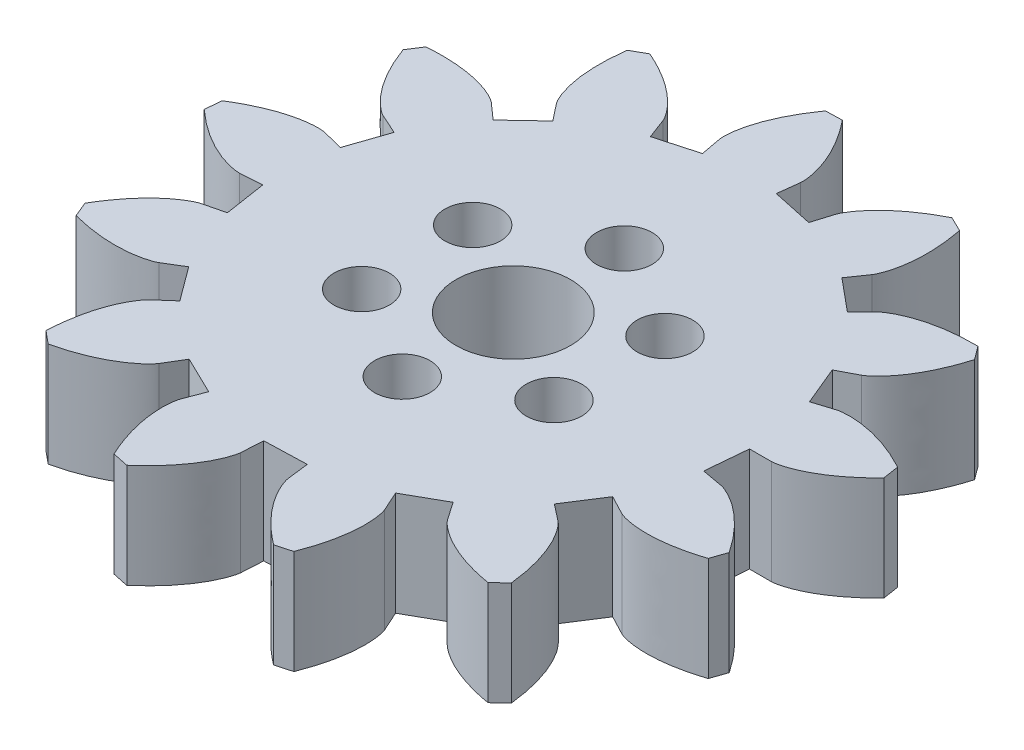
SolidWorks part; units mm, degrees
ref_plane "Front Plane" through (0, 0, 0) normal (0, 0, 1) x (1, 0, 0)
ref_plane "Top Plane" through (0, 0, 0) normal (0, 1, 0) x (1, 0, 0)
ref_plane "Right Plane" through (0, 0, 0) normal (1, 0, 0) x (0, 0, -1)
sketch "Sketch1" plane through (0, 0, 0) normal (0, 1, 0) x (1, 0, 0)
  circle A0 centre (0, 0) radius 8.2743 construction
  circle A1 centre (0, 0) radius 8.2743
  circle A3 centre (-2.7713, -1.6) radius 0.8
  circle A4 centre (-2.7713, -1.6) radius 0.8
  circle A5 centre (0, -3.2) radius 0.8
  circle A6 centre (0, -3.2) radius 0.8
  circle A7 centre (2.7713, -1.6) radius 0.8
  circle A8 centre (2.7713, -1.6) radius 0.8
  circle A9 centre (2.7713, 1.6) radius 0.8
  circle A10 centre (2.7713, 1.6) radius 0.8
  circle A11 centre (0, 3.2) radius 0.8
  circle A12 centre (0, 3.2) radius 0.8
  circle A13 centre (-2.7713, 1.6) radius 0.8
  circle A14 centre (-2.7713, 1.6) radius 0.8
  dimension "D1" = 0
  dimension "D2" = 0
  dimension "D3" = 0
  dimension "D4" = 0
  dimension "D5" = 0
  dimension "D6" = 0
sketch "Sketch2" plane through (0, 0, 0) normal (0, 1, 0) x (1, 0, 0)
  line L0 (6.8098, 0) -> (7.4374, 0)
  line L1 (7.4374, 0) -> (7.4435, 0.0002)
  line L2 (7.4435, 0.0002) -> (7.455, 0.0009)
  line L3 (7.455, 0.0009) -> (7.4719, 0.0023)
  line L4 (7.4719, 0.0023) -> (7.494, 0.0048)
  line L5 (7.494, 0.0048) -> (7.5213, 0.0086)
  line L6 (7.5213, 0.0086) -> (7.5538, 0.0141)
  line L7 (7.5538, 0.0141) -> (7.5915, 0.0214)
  line L8 (7.5915, 0.0214) -> (7.6341, 0.0309)
  line L9 (7.6341, 0.0309) -> (7.6817, 0.0428)
  line L10 (7.6817, 0.0428) -> (7.7341, 0.0575)
  line L11 (7.7341, 0.0575) -> (7.7912, 0.0751)
  line L12 (7.7912, 0.0751) -> (7.8529, 0.096)
  line L13 (7.8529, 0.096) -> (7.9191, 0.1204)
  line L14 (7.9191, 0.1204) -> (7.9895, 0.1486)
  line L15 (7.9895, 0.1486) -> (8.0641, 0.1807)
  line L16 (8.0641, 0.1807) -> (8.1427, 0.2171)
  line L17 (8.1427, 0.2171) -> (8.225, 0.258)
  line L18 (8.225, 0.258) -> (8.311, 0.3036)
  line L19 (8.311, 0.3036) -> (8.4004, 0.3541)
  line L20 (8.4004, 0.3541) -> (8.493, 0.4097)
  line L21 (8.493, 0.4097) -> (8.5886, 0.4707)
  line L22 (8.5886, 0.4707) -> (8.6869, 0.5373)
  line L23 (8.6869, 0.5373) -> (8.7878, 0.6095)
  line L24 (8.7878, 0.6095) -> (8.891, 0.6877)
  line L25 (8.891, 0.6877) -> (8.9962, 0.772)
  line L26 (8.9962, 0.772) -> (9.1033, 0.8626)
  line L27 (9.1033, 0.8626) -> (9.2118, 0.9596)
  line L28 (9.2118, 0.9596) -> (9.3216, 1.0631)
  line L29 (9.3216, 1.0631) -> (9.4324, 1.1733)
  line L30 (9.4324, 1.1733) -> (9.4602, 1.2019)
  line L31 (9.4602, 1.2019) -> (9.4672, 1.2092)
  line L32 (9.4672, 1.2092) -> (9.4689, 1.211)
  line L33 (9.4689, 1.211) -> (9.4692, 1.2112)
  line L34 (9.4692, 1.2112) -> (9.4693, 1.2114)
  line L35 (9.4693, 1.2114) -> (9.3971, 1.6821)
  line L36 (9.3971, 1.6821) -> (9.3969, 1.6823)
  line L37 (9.3969, 1.6823) -> (9.3966, 1.6825)
  line L38 (9.3966, 1.6825) -> (9.3944, 1.6837)
  line L39 (9.3944, 1.6837) -> (9.3856, 1.6885)
  line L40 (9.3856, 1.6885) -> (9.3505, 1.7074)
  line L41 (9.3505, 1.7074) -> (9.2118, 1.7794)
  line L42 (9.2118, 1.7794) -> (9.076, 1.8452)
  line L43 (9.076, 1.8452) -> (8.9434, 1.9052)
  line L44 (8.9434, 1.9052) -> (8.8141, 1.9595)
  line L45 (8.8141, 1.9595) -> (8.6884, 2.0084)
  line L46 (8.6884, 2.0084) -> (8.5666, 2.0521)
  line L47 (8.5666, 2.0521) -> (8.4487, 2.0908)
  line L48 (8.4487, 2.0908) -> (8.3349, 2.1248)
  line L49 (8.3349, 2.1248) -> (8.2254, 2.1544)
  line L50 (8.2254, 2.1544) -> (8.1204, 2.1797)
  line L51 (8.1204, 2.1797) -> (8.02, 2.2011)
  line L52 (8.02, 2.2011) -> (7.9243, 2.2189)
  line L53 (7.9243, 2.2189) -> (7.8335, 2.2332)
  line L54 (7.8335, 2.2332) -> (7.7476, 2.2443)
  line L55 (7.7476, 2.2443) -> (7.6668, 2.2527)
  line L56 (7.6668, 2.2527) -> (7.5912, 2.2584)
  line L57 (7.5912, 2.2584) -> (7.5207, 2.2618)
  line L58 (7.5207, 2.2618) -> (7.4556, 2.2633)
  line L59 (7.4556, 2.2633) -> (7.3958, 2.263)
  line L60 (7.3958, 2.263) -> (7.3415, 2.2613)
  line L61 (7.3415, 2.2613) -> (7.2925, 2.2584)
  line L62 (7.2925, 2.2584) -> (7.2489, 2.2547)
  line L63 (7.2489, 2.2547) -> (7.2109, 2.2504)
  line L64 (7.2109, 2.2504) -> (7.1782, 2.2458)
  line L65 (7.1782, 2.2458) -> (7.151, 2.2413)
  line L66 (7.151, 2.2413) -> (7.1291, 2.237)
  line L67 (7.1291, 2.237) -> (7.1126, 2.2334)
  line L68 (7.1126, 2.2334) -> (7.1015, 2.2306)
  line L69 (7.1015, 2.2306) -> (7.0955, 2.2289)
  line L70 (7.0955, 2.2289) -> (6.4968, 2.0408)
  line L71 (6.4968, 2.0408) -> (6.0298, 3.1647)
  line L72 (6.0298, 3.1647) -> (6.5855, 3.4563)
  line L73 (6.5855, 3.4563) -> (6.5908, 3.4594)
  line L74 (6.5908, 3.4594) -> (6.6007, 3.4653)
  line L75 (6.6007, 3.4653) -> (6.6149, 3.4744)
  line L76 (6.6149, 3.4744) -> (6.6333, 3.4869)
  line L77 (6.6333, 3.4869) -> (6.6558, 3.503)
  line L78 (6.6558, 3.503) -> (6.6821, 3.5229)
  line L79 (6.6821, 3.5229) -> (6.712, 3.5469)
  line L80 (6.712, 3.5469) -> (6.7453, 3.5751)
  line L81 (6.7453, 3.5751) -> (6.7819, 3.6078)
  line L82 (6.7819, 3.6078) -> (6.8215, 3.6451)
  line L83 (6.8215, 3.6451) -> (6.8639, 3.6873)
  line L84 (6.8639, 3.6873) -> (6.9088, 3.7345)
  line L85 (6.9088, 3.7345) -> (6.956, 3.7868)
  line L86 (6.956, 3.7868) -> (7.0053, 3.8445)
  line L87 (7.0053, 3.8445) -> (7.0564, 3.9076)
  line L88 (7.0564, 3.9076) -> (7.1091, 3.9763)
  line L89 (7.1091, 3.9763) -> (7.163, 4.0508)
  line L90 (7.163, 4.0508) -> (7.218, 4.1311)
  line L91 (7.218, 4.1311) -> (7.2736, 4.2174)
  line L92 (7.2736, 4.2174) -> (7.3298, 4.3097)
  line L93 (7.3298, 4.3097) -> (7.3861, 4.4081)
  line L94 (7.3861, 4.4081) -> (7.4422, 4.5127)
  line L95 (7.4422, 4.5127) -> (7.498, 4.6236)
  line L96 (7.498, 4.6236) -> (7.553, 4.7408)
  line L97 (7.553, 4.7408) -> (7.607, 4.8644)
  line L98 (7.607, 4.8644) -> (7.6597, 4.9943)
  line L99 (7.6597, 4.9943) -> (7.7107, 5.1306)
  line L100 (7.7107, 5.1306) -> (7.7598, 5.2733)
  line L101 (7.7598, 5.2733) -> (7.8067, 5.4224)
  line L102 (7.8067, 5.4224) -> (7.8181, 5.4607)
  line L103 (7.8181, 5.4607) -> (7.8209, 5.4703)
  line L104 (7.8209, 5.4703) -> (7.8216, 5.4727)
  line L105 (7.8216, 5.4727) -> (7.8217, 5.473)
  line L106 (7.8217, 5.473) -> (7.8216, 5.4732)
  line L107 (7.8216, 5.4732) -> (7.539, 5.8565)
  line L108 (7.539, 5.8565) -> (7.5387, 5.8566)
  line L109 (7.5387, 5.8566) -> (7.5384, 5.8566)
  line L110 (7.5384, 5.8566) -> (7.5359, 5.8566)
  line L111 (7.5359, 5.8566) -> (7.5259, 5.8568)
  line L112 (7.5259, 5.8568) -> (7.486, 5.8572)
  line L113 (7.486, 5.8572) -> (7.3297, 5.8565)
  line L114 (7.3297, 5.8565) -> (7.1789, 5.8517)
  line L115 (7.1789, 5.8517) -> (7.0336, 5.8432)
  line L116 (7.0336, 5.8432) -> (6.8939, 5.8312)
  line L117 (6.8939, 5.8312) -> (6.7599, 5.8161)
  line L118 (6.7599, 5.8161) -> (6.6317, 5.7981)
  line L119 (6.6317, 5.7981) -> (6.5093, 5.7776)
  line L120 (6.5093, 5.7776) -> (6.3927, 5.7549)
  line L121 (6.3927, 5.7549) -> (6.282, 5.7302)
  line L122 (6.282, 5.7302) -> (6.1773, 5.7038)
  line L123 (6.1773, 5.7038) -> (6.0784, 5.6761)
  line L124 (6.0784, 5.6761) -> (5.9855, 5.6473)
  line L125 (5.9855, 5.6473) -> (5.8984, 5.6178)
  line L126 (5.8984, 5.6178) -> (5.8172, 5.5878)
  line L127 (5.8172, 5.5878) -> (5.7418, 5.5576)
  line L128 (5.7418, 5.5576) -> (5.6721, 5.5275)
  line L129 (5.6721, 5.5275) -> (5.6082, 5.4978)
  line L130 (5.6082, 5.4978) -> (5.5498, 5.4688)
  line L131 (5.5498, 5.4688) -> (5.497, 5.4408)
  line L132 (5.497, 5.4408) -> (5.4497, 5.414)
  line L133 (5.4497, 5.414) -> (5.4076, 5.3887)
  line L134 (5.4076, 5.3887) -> (5.3708, 5.3652)
  line L135 (5.3708, 5.3652) -> (5.3391, 5.3437)
  line L136 (5.3391, 5.3437) -> (5.3123, 5.3245)
  line L137 (5.3123, 5.3245) -> (5.2903, 5.3078)
  line L138 (5.2903, 5.3078) -> (5.2729, 5.2939)
  line L139 (5.2729, 5.2939) -> (5.26, 5.283)
  line L140 (5.26, 5.283) -> (5.2514, 5.2753)
  line L141 (5.2514, 5.2753) -> (5.247, 5.2711)
  line L142 (5.247, 5.2711) -> (4.8042, 4.8263)
  line L143 (4.8042, 4.8263) -> (3.8684, 5.6043)
  line L144 (3.8684, 5.6043) -> (4.2249, 6.1208)
  line L145 (4.2249, 6.1208) -> (4.2282, 6.126)
  line L146 (4.2282, 6.126) -> (4.2342, 6.1359)
  line L147 (4.2342, 6.1359) -> (4.2426, 6.1505)
  line L148 (4.2426, 6.1505) -> (4.2531, 6.1702)
  line L149 (4.2531, 6.1702) -> (4.2655, 6.1948)
  line L150 (4.2655, 6.1948) -> (4.2795, 6.2247)
  line L151 (4.2795, 6.2247) -> (4.2948, 6.2598)
  line L152 (4.2948, 6.2598) -> (4.3112, 6.3003)
  line L153 (4.3112, 6.3003) -> (4.3284, 6.3462)
  line L154 (4.3284, 6.3462) -> (4.3462, 6.3977)
  line L155 (4.3462, 6.3977) -> (4.3641, 6.4547)
  line L156 (4.3641, 6.4547) -> (4.3819, 6.5174)
  line L157 (4.3819, 6.5174) -> (4.3994, 6.5857)
  line L158 (4.3994, 6.5857) -> (4.4163, 6.6596)
  line L159 (4.4163, 6.6596) -> (4.4322, 6.7393)
  line L160 (4.4322, 6.7393) -> (4.4469, 6.8246)
  line L161 (4.4469, 6.8246) -> (4.46, 6.9156)
  line L162 (4.46, 6.9156) -> (4.4714, 7.0123)
  line L163 (4.4714, 7.0123) -> (4.4806, 7.1145)
  line L164 (4.4806, 7.1145) -> (4.4874, 7.2223)
  line L165 (4.4874, 7.2223) -> (4.4915, 7.3356)
  line L166 (4.4915, 7.3356) -> (4.4926, 7.4544)
  line L167 (4.4926, 7.4544) -> (4.4904, 7.5785)
  line L168 (4.4904, 7.5785) -> (4.4847, 7.7078)
  line L169 (4.4847, 7.7078) -> (4.4751, 7.8423)
  line L170 (4.4751, 7.8423) -> (4.4613, 7.9819)
  line L171 (4.4613, 7.9819) -> (4.4432, 8.1263)
  line L172 (4.4432, 8.1263) -> (4.4204, 8.2755)
  line L173 (4.4204, 8.2755) -> (4.3926, 8.4293)
  line L174 (4.3926, 8.4293) -> (4.3849, 8.4684)
  line L175 (4.3849, 8.4684) -> (4.3829, 8.4782)
  line L176 (4.3829, 8.4782) -> (4.3824, 8.4807)
  line L177 (4.3824, 8.4807) -> (4.3823, 8.481)
  line L178 (4.3823, 8.481) -> (4.3822, 8.4812)
  line L179 (4.3822, 8.4812) -> (3.9538, 8.6892)
  line L180 (3.9538, 8.6892) -> (3.9535, 8.6892)
  line L181 (3.9535, 8.6892) -> (3.9533, 8.689)
  line L182 (3.9533, 8.689) -> (3.951, 8.6879)
  line L183 (3.951, 8.6879) -> (3.9421, 8.6834)
  line L184 (3.9421, 8.6834) -> (3.9065, 8.6652)
  line L185 (3.9065, 8.6652) -> (3.7685, 8.5919)
  line L186 (3.7685, 8.5919) -> (3.6371, 8.5176)
  line L187 (3.6371, 8.5176) -> (3.5125, 8.4425)
  line L188 (3.5125, 8.4425) -> (3.3943, 8.367)
  line L189 (3.3943, 8.367) -> (3.2827, 8.2914)
  line L190 (3.2827, 8.2914) -> (3.1775, 8.2159)
  line L191 (3.1775, 8.2159) -> (3.0787, 8.1408)
  line L192 (3.0787, 8.1408) -> (2.986, 8.0665)
  line L193 (2.986, 8.0665) -> (2.8995, 7.9932)
  line L194 (2.8995, 7.9932) -> (2.819, 7.9212)
  line L195 (2.819, 7.9212) -> (2.7444, 7.8507)
  line L196 (2.7444, 7.8507) -> (2.6754, 7.782)
  line L197 (2.6754, 7.782) -> (2.6121, 7.7154)
  line L198 (2.6121, 7.7154) -> (2.5541, 7.6511)
  line L199 (2.5541, 7.6511) -> (2.5013, 7.5893)
  line L200 (2.5013, 7.5893) -> (2.4537, 7.5303)
  line L201 (2.4537, 7.5303) -> (2.4108, 7.4743)
  line L202 (2.4108, 7.4743) -> (2.3726, 7.4215)
  line L203 (2.3726, 7.4215) -> (2.3389, 7.3722)
  line L204 (2.3389, 7.3722) -> (2.3094, 7.3265)
  line L205 (2.3094, 7.3265) -> (2.284, 7.2845)
  line L206 (2.284, 7.2845) -> (2.2623, 7.2466)
  line L207 (2.2623, 7.2466) -> (2.2442, 7.2128)
  line L208 (2.2442, 7.2128) -> (2.2294, 7.1833)
  line L209 (2.2294, 7.1833) -> (2.2177, 7.1583)
  line L210 (2.2177, 7.1583) -> (2.2088, 7.1379)
  line L211 (2.2088, 7.1379) -> (2.2024, 7.1223)
  line L212 (2.2024, 7.1223) -> (2.1984, 7.1115)
  line L213 (2.1984, 7.1115) -> (2.1964, 7.1057)
  line L214 (2.1964, 7.1057) -> (2.011, 6.5061)
  line L215 (2.011, 6.5061) -> (0.8208, 6.7601)
  line L216 (0.8208, 6.7601) -> (0.8965, 7.3831)
  line L217 (0.8965, 7.3831) -> (0.897, 7.3893)
  line L218 (0.897, 7.3893) -> (0.8977, 7.4008)
  line L219 (0.8977, 7.4008) -> (0.8983, 7.4177)
  line L220 (0.8983, 7.4177) -> (0.8985, 7.4399)
  line L221 (0.8985, 7.4399) -> (0.898, 7.4675)
  line L222 (0.898, 7.4675) -> (0.8965, 7.5005)
  line L223 (0.8965, 7.5005) -> (0.8938, 7.5387)
  line L224 (0.8938, 7.5387) -> (0.8895, 7.5822)
  line L225 (0.8895, 7.5822) -> (0.8834, 7.6309)
  line L226 (0.8834, 7.6309) -> (0.8752, 7.6846)
  line L227 (0.8752, 7.6846) -> (0.8645, 7.7435)
  line L228 (0.8645, 7.7435) -> (0.8512, 7.8072)
  line L229 (0.8512, 7.8072) -> (0.835, 7.8758)
  line L230 (0.835, 7.8758) -> (0.8156, 7.9492)
  line L231 (0.8156, 7.9492) -> (0.7926, 8.0271)
  line L232 (0.7926, 8.0271) -> (0.766, 8.1095)
  line L233 (0.766, 8.1095) -> (0.7353, 8.1962)
  line L234 (0.7353, 8.1962) -> (0.7004, 8.287)
  line L235 (0.7004, 8.287) -> (0.6611, 8.3818)
  line L236 (0.6611, 8.3818) -> (0.617, 8.4804)
  line L237 (0.617, 8.4804) -> (0.568, 8.5827)
  line L238 (0.568, 8.5827) -> (0.5138, 8.6883)
  line L239 (0.5138, 8.6883) -> (0.4542, 8.7972)
  line L240 (0.4542, 8.7972) -> (0.389, 8.9091)
  line L241 (0.389, 8.9091) -> (0.318, 9.0237)
  line L242 (0.318, 9.0237) -> (0.241, 9.1409)
  line L243 (0.241, 9.1409) -> (0.1578, 9.2603)
  line L244 (0.1578, 9.2603) -> (0.0682, 9.3818)
  line L245 (0.0682, 9.3818) -> (-0.0278, 9.5051)
  line L246 (-0.0278, 9.5051) -> (-0.0529, 9.5361)
  line L247 (-0.0529, 9.5361) -> (-0.0592, 9.5439)
  line L248 (-0.0592, 9.5439) -> (-0.0608, 9.5459)
  line L249 (-0.0608, 9.5459) -> (-0.061, 9.5461)
  line L250 (-0.061, 9.5461) -> (-0.0612, 9.5462)
  line L251 (-0.0612, 9.5462) -> (-0.5372, 9.5313)
  line L252 (-0.5372, 9.5313) -> (-0.5374, 9.5312)
  line L253 (-0.5374, 9.5312) -> (-0.5375, 9.5309)
  line L254 (-0.5375, 9.5309) -> (-0.539, 9.5289)
  line L255 (-0.539, 9.5289) -> (-0.5448, 9.5207)
  line L256 (-0.5448, 9.5207) -> (-0.5679, 9.4881)
  line L257 (-0.5679, 9.4881) -> (-0.656, 9.3591)
  line L258 (-0.656, 9.3591) -> (-0.7378, 9.2322)
  line L259 (-0.7378, 9.2322) -> (-0.8133, 9.1078)
  line L260 (-0.8133, 9.1078) -> (-0.8828, 8.986)
  line L261 (-0.8828, 8.986) -> (-0.9465, 8.8672)
  line L262 (-0.9465, 8.8672) -> (-1.0046, 8.7515)
  line L263 (-1.0046, 8.7515) -> (-1.0572, 8.6391)
  line L264 (-1.0572, 8.6391) -> (-1.1047, 8.5302)
  line L265 (-1.1047, 8.5302) -> (-1.1472, 8.4251)
  line L266 (-1.1472, 8.4251) -> (-1.185, 8.3239)
  line L267 (-1.185, 8.3239) -> (-1.2184, 8.2268)
  line L268 (-1.2184, 8.2268) -> (-1.2475, 8.134)
  line L269 (-1.2475, 8.134) -> (-1.2727, 8.0455)
  line L270 (-1.2727, 8.0455) -> (-1.2941, 7.9616)
  line L271 (-1.2941, 7.9616) -> (-1.3121, 7.8824)
  line L272 (-1.3121, 7.8824) -> (-1.3269, 7.808)
  line L273 (-1.3269, 7.808) -> (-1.3388, 7.7385)
  line L274 (-1.3388, 7.7385) -> (-1.3481, 7.6741)
  line L275 (-1.3481, 7.6741) -> (-1.355, 7.6147)
  line L276 (-1.355, 7.6147) -> (-1.3599, 7.5605)
  line L277 (-1.3599, 7.5605) -> (-1.3629, 7.5115)
  line L278 (-1.3629, 7.5115) -> (-1.3645, 7.4679)
  line L279 (-1.3645, 7.4679) -> (-1.3648, 7.4295)
  line L280 (-1.3648, 7.4295) -> (-1.3642, 7.3966)
  line L281 (-1.3642, 7.3966) -> (-1.363, 7.369)
  line L282 (-1.363, 7.369) -> (-1.3614, 7.3468)
  line L283 (-1.3614, 7.3468) -> (-1.3597, 7.33)
  line L284 (-1.3597, 7.33) -> (-1.3583, 7.3186)
  line L285 (-1.3583, 7.3186) -> (-1.3574, 7.3125)
  line L286 (-1.3574, 7.3125) -> (-1.2429, 6.6954)
  line L287 (-1.2429, 6.6954) -> (-2.4148, 6.3673)
  line L288 (-2.4148, 6.3673) -> (-2.6373, 6.9541)
  line L289 (-2.6373, 6.9541) -> (-2.6397, 6.9598)
  line L290 (-2.6397, 6.9598) -> (-2.6444, 6.9703)
  line L291 (-2.6444, 6.9703) -> (-2.6517, 6.9855)
  line L292 (-2.6517, 6.9855) -> (-2.6619, 7.0053)
  line L293 (-2.6619, 7.0053) -> (-2.6752, 7.0295)
  line L294 (-2.6752, 7.0295) -> (-2.6918, 7.058)
  line L295 (-2.6918, 7.058) -> (-2.712, 7.0906)
  line L296 (-2.712, 7.0906) -> (-2.736, 7.1271)
  line L297 (-2.736, 7.1271) -> (-2.764, 7.1673)
  line L298 (-2.764, 7.1673) -> (-2.7963, 7.2111)
  line L299 (-2.7963, 7.2111) -> (-2.8331, 7.2583)
  line L300 (-2.8331, 7.2583) -> (-2.8745, 7.3086)
  line L301 (-2.8745, 7.3086) -> (-2.9207, 7.3618)
  line L302 (-2.9207, 7.3618) -> (-2.972, 7.4176)
  line L303 (-2.972, 7.4176) -> (-3.0285, 7.476)
  line L304 (-3.0285, 7.476) -> (-3.0904, 7.5365)
  line L305 (-3.0904, 7.5365) -> (-3.1578, 7.5991)
  line L306 (-3.1578, 7.5991) -> (-3.2309, 7.6633)
  line L307 (-3.2309, 7.6633) -> (-3.3099, 7.729)
  line L308 (-3.3099, 7.729) -> (-3.3947, 7.7958)
  line L309 (-3.3947, 7.7958) -> (-3.4857, 7.8635)
  line L310 (-3.4857, 7.8635) -> (-3.5828, 7.9319)
  line L311 (-3.5828, 7.9319) -> (-3.6861, 8.0006)
  line L312 (-3.6861, 8.0006) -> (-3.7958, 8.0694)
  line L313 (-3.7958, 8.0694) -> (-3.912, 8.1379)
  line L314 (-3.912, 8.1379) -> (-4.0346, 8.2058)
  line L315 (-4.0346, 8.2058) -> (-4.1638, 8.2729)
  line L316 (-4.1638, 8.2729) -> (-4.2995, 8.3389)
  line L317 (-4.2995, 8.3389) -> (-4.4419, 8.4034)
  line L318 (-4.4419, 8.4034) -> (-4.4785, 8.4193)
  line L319 (-4.4785, 8.4193) -> (-4.4877, 8.4232)
  line L320 (-4.4877, 8.4232) -> (-4.49, 8.4242)
  line L321 (-4.49, 8.4242) -> (-4.4903, 8.4243)
  line L322 (-4.4903, 8.4243) -> (-4.4905, 8.4243)
  line L323 (-4.4905, 8.4243) -> (-4.9051, 8.1899)
  line L324 (-4.9051, 8.1899) -> (-4.9052, 8.1897)
  line L325 (-4.9052, 8.1897) -> (-4.9052, 8.1894)
  line L326 (-4.9052, 8.1894) -> (-4.9056, 8.1869)
  line L327 (-4.9056, 8.1869) -> (-4.9069, 8.177)
  line L328 (-4.9069, 8.177) -> (-4.9122, 8.1374)
  line L329 (-4.9122, 8.1374) -> (-4.9303, 7.9822)
  line L330 (-4.9303, 7.9822) -> (-4.9437, 7.8319)
  line L331 (-4.9437, 7.8319) -> (-4.9528, 7.6866)
  line L332 (-4.9528, 7.6866) -> (-4.9577, 7.5465)
  line L333 (-4.9577, 7.5465) -> (-4.9589, 7.4116)
  line L334 (-4.9589, 7.4116) -> (-4.9565, 7.2822)
  line L335 (-4.9565, 7.2822) -> (-4.9509, 7.1582)
  line L336 (-4.9509, 7.1582) -> (-4.9424, 7.0398)
  line L337 (-4.9424, 7.0398) -> (-4.9312, 6.9269)
  line L338 (-4.9312, 6.9269) -> (-4.9176, 6.8197)
  line L339 (-4.9176, 6.8197) -> (-4.902, 6.7183)
  line L340 (-4.902, 6.7183) -> (-4.8847, 6.6225)
  line L341 (-4.8847, 6.6225) -> (-4.8658, 6.5325)
  line L342 (-4.8658, 6.5325) -> (-4.8458, 6.4483)
  line L343 (-4.8458, 6.4483) -> (-4.825, 6.3698)
  line L344 (-4.825, 6.3698) -> (-4.8035, 6.297)
  line L345 (-4.8035, 6.297) -> (-4.7818, 6.23)
  line L346 (-4.7818, 6.23) -> (-4.76, 6.1686)
  line L347 (-4.76, 6.1686) -> (-4.7385, 6.1128)
  line L348 (-4.7385, 6.1128) -> (-4.7176, 6.0625)
  line L349 (-4.7176, 6.0625) -> (-4.6976, 6.0177)
  line L350 (-4.6976, 6.0177) -> (-4.6787, 5.9784)
  line L351 (-4.6787, 5.9784) -> (-4.6612, 5.9443)
  line L352 (-4.6612, 5.9443) -> (-4.6453, 5.9154)
  line L353 (-4.6453, 5.9154) -> (-4.6314, 5.8915)
  line L354 (-4.6314, 5.8915) -> (-4.6197, 5.8726)
  line L355 (-4.6197, 5.8726) -> (-4.6104, 5.8585)
  line L356 (-4.6104, 5.8585) -> (-4.6038, 5.849)
  line L357 (-4.6038, 5.849) -> (-4.6002, 5.8441)
  line L358 (-4.6002, 5.8441) -> (-4.212, 5.3509)
  line L359 (-4.212, 5.3509) -> (-5.0972, 4.5157)
  line L360 (-5.0972, 4.5157) -> (-5.567, 4.9319)
  line L361 (-5.567, 4.9319) -> (-5.5717, 4.9358)
  line L362 (-5.5717, 4.9358) -> (-5.5808, 4.9429)
  line L363 (-5.5808, 4.9429) -> (-5.5943, 4.953)
  line L364 (-5.5943, 4.953) -> (-5.6125, 4.9658)
  line L365 (-5.6125, 4.9658) -> (-5.6355, 4.9811)
  line L366 (-5.6355, 4.9811) -> (-5.6635, 4.9986)
  line L367 (-5.6635, 4.9986) -> (-5.6965, 5.0181)
  line L368 (-5.6965, 5.0181) -> (-5.7347, 5.0392)
  line L369 (-5.7347, 5.0392) -> (-5.7782, 5.0618)
  line L370 (-5.7782, 5.0618) -> (-5.8272, 5.0856)
  line L371 (-5.8272, 5.0856) -> (-5.8816, 5.1103)
  line L372 (-5.8816, 5.1103) -> (-5.9417, 5.1356)
  line L373 (-5.9417, 5.1356) -> (-6.0074, 5.1612)
  line L374 (-6.0074, 5.1612) -> (-6.0787, 5.1868)
  line L375 (-6.0787, 5.1868) -> (-6.1559, 5.2122)
  line L376 (-6.1559, 5.2122) -> (-6.2388, 5.2371)
  line L377 (-6.2388, 5.2371) -> (-6.3276, 5.2611)
  line L378 (-6.3276, 5.2611) -> (-6.4222, 5.284)
  line L379 (-6.4222, 5.284) -> (-6.5226, 5.3055)
  line L380 (-6.5226, 5.3055) -> (-6.6288, 5.3252)
  line L381 (-6.6288, 5.3252) -> (-6.7408, 5.3429)
  line L382 (-6.7408, 5.3429) -> (-6.8585, 5.3584)
  line L383 (-6.8585, 5.3584) -> (-6.982, 5.3712)
  line L384 (-6.982, 5.3712) -> (-7.1111, 5.381)
  line L385 (-7.1111, 5.381) -> (-7.2457, 5.3877)
  line L386 (-7.2457, 5.3877) -> (-7.3859, 5.3909)
  line L387 (-7.3859, 5.3909) -> (-7.5315, 5.3903)
  line L388 (-7.5315, 5.3903) -> (-7.6823, 5.3856)
  line L389 (-7.6823, 5.3856) -> (-7.8383, 5.3766)
  line L390 (-7.8383, 5.3766) -> (-7.8781, 5.3736)
  line L391 (-7.8781, 5.3736) -> (-7.8881, 5.3729)
  line L392 (-7.8881, 5.3729) -> (-7.8906, 5.3727)
  line L393 (-7.8906, 5.3727) -> (-7.8909, 5.3726)
  line L394 (-7.8909, 5.3726) -> (-7.8912, 5.3725)
  line L395 (-7.8912, 5.3725) -> (-8.1493, 4.9723)
  line L396 (-8.1493, 4.9723) -> (-8.1493, 4.9721)
  line L397 (-8.1493, 4.9721) -> (-8.1492, 4.9718)
  line L398 (-8.1492, 4.9718) -> (-8.1483, 4.9694)
  line L399 (-8.1483, 4.9694) -> (-8.1449, 4.96)
  line L400 (-8.1449, 4.96) -> (-8.1312, 4.9225)
  line L401 (-8.1312, 4.9225) -> (-8.0751, 4.7767)
  line L402 (-8.0751, 4.7767) -> (-8.0171, 4.6373)
  line L403 (-8.0171, 4.6373) -> (-7.9576, 4.5045)
  line L404 (-7.9576, 4.5045) -> (-7.8969, 4.3781)
  line L405 (-7.8969, 4.3781) -> (-7.8352, 4.2582)
  line L406 (-7.8352, 4.2582) -> (-7.773, 4.1447)
  line L407 (-7.773, 4.1447) -> (-7.7104, 4.0375)
  line L408 (-7.7104, 4.0375) -> (-7.6478, 3.9366)
  line L409 (-7.6478, 3.9366) -> (-7.5854, 3.8419)
  line L410 (-7.5854, 3.8419) -> (-7.5236, 3.7533)
  line L411 (-7.5236, 3.7533) -> (-7.4627, 3.6707)
  line L412 (-7.4627, 3.6707) -> (-7.4028, 3.5939)
  line L413 (-7.4028, 3.5939) -> (-7.3443, 3.523)
  line L414 (-7.3443, 3.523) -> (-7.2874, 3.4577)
  line L415 (-7.2874, 3.4577) -> (-7.2325, 3.3979)
  line L416 (-7.2325, 3.3979) -> (-7.1797, 3.3434)
  line L417 (-7.1797, 3.3434) -> (-7.1292, 3.2942)
  line L418 (-7.1292, 3.2942) -> (-7.0814, 3.2499)
  line L419 (-7.0814, 3.2499) -> (-7.0365, 3.2105)
  line L420 (-7.0365, 3.2105) -> (-6.9947, 3.1757)
  line L421 (-6.9947, 3.1757) -> (-6.9561, 3.1454)
  line L422 (-6.9561, 3.1454) -> (-6.9211, 3.1193)
  line L423 (-6.9211, 3.1193) -> (-6.8897, 3.0972)
  line L424 (-6.8897, 3.0972) -> (-6.8622, 3.079)
  line L425 (-6.8622, 3.079) -> (-6.8388, 3.0643)
  line L426 (-6.8388, 3.0643) -> (-6.8197, 3.0531)
  line L427 (-6.8197, 3.0531) -> (-6.8049, 3.0449)
  line L428 (-6.8049, 3.0449) -> (-6.7947, 3.0395)
  line L429 (-6.7947, 3.0395) -> (-6.7891, 3.0368)
  line L430 (-6.7891, 3.0368) -> (-6.2162, 2.7806)
  line L431 (-6.2162, 2.7806) -> (-6.6119, 1.6297)
  line L432 (-6.6119, 1.6297) -> (-7.2213, 1.7799)
  line L433 (-7.2213, 1.7799) -> (-7.2273, 1.7811)
  line L434 (-7.2273, 1.7811) -> (-7.2386, 1.7832)
  line L435 (-7.2386, 1.7832) -> (-7.2553, 1.7859)
  line L436 (-7.2553, 1.7859) -> (-7.2774, 1.7887)
  line L437 (-7.2774, 1.7887) -> (-7.3048, 1.7916)
  line L438 (-7.3048, 1.7916) -> (-7.3377, 1.7941)
  line L439 (-7.3377, 1.7941) -> (-7.376, 1.796)
  line L440 (-7.376, 1.796) -> (-7.4197, 1.797)
  line L441 (-7.4197, 1.797) -> (-7.4687, 1.7968)
  line L442 (-7.4687, 1.7968) -> (-7.5231, 1.7951)
  line L443 (-7.5231, 1.7951) -> (-7.5828, 1.7916)
  line L444 (-7.5828, 1.7916) -> (-7.6477, 1.7861)
  line L445 (-7.6477, 1.7861) -> (-7.7178, 1.7782)
  line L446 (-7.7178, 1.7782) -> (-7.7929, 1.7678)
  line L447 (-7.7929, 1.7678) -> (-7.873, 1.7544)
  line L448 (-7.873, 1.7544) -> (-7.958, 1.7379)
  line L449 (-7.958, 1.7379) -> (-8.0478, 1.7179)
  line L450 (-8.0478, 1.7179) -> (-8.1421, 1.6942)
  line L451 (-8.1421, 1.6942) -> (-8.241, 1.6666)
  line L452 (-8.241, 1.6666) -> (-8.3442, 1.6347)
  line L453 (-8.3442, 1.6347) -> (-8.4517, 1.5984)
  line L454 (-8.4517, 1.5984) -> (-8.5631, 1.5573)
  line L455 (-8.5631, 1.5573) -> (-8.6783, 1.5112)
  line L456 (-8.6783, 1.5112) -> (-8.7972, 1.46)
  line L457 (-8.7972, 1.46) -> (-8.9196, 1.4033)
  line L458 (-8.9196, 1.4033) -> (-9.0452, 1.341)
  line L459 (-9.0452, 1.341) -> (-9.1738, 1.2728)
  line L460 (-9.1738, 1.2728) -> (-9.3052, 1.1986)
  line L461 (-9.3052, 1.1986) -> (-9.4391, 1.1181)
  line L462 (-9.4391, 1.1181) -> (-9.473, 1.097)
  line L463 (-9.473, 1.097) -> (-9.4815, 1.0916)
  line L464 (-9.4815, 1.0916) -> (-9.4836, 1.0903)
  line L465 (-9.4836, 1.0903) -> (-9.4839, 1.0901)
  line L466 (-9.4839, 1.0901) -> (-9.484, 1.0899)
  line L467 (-9.484, 1.0899) -> (-9.5266, 0.6156)
  line L468 (-9.5266, 0.6156) -> (-9.5265, 0.6154)
  line L469 (-9.5265, 0.6154) -> (-9.5262, 0.6152)
  line L470 (-9.5262, 0.6152) -> (-9.5244, 0.6135)
  line L471 (-9.5244, 0.6135) -> (-9.517, 0.6067)
  line L472 (-9.517, 0.6067) -> (-9.4874, 0.5799)
  line L473 (-9.4874, 0.5799) -> (-9.3699, 0.4769)
  line L474 (-9.3699, 0.4769) -> (-9.2538, 0.3804)
  line L475 (-9.2538, 0.3804) -> (-9.1394, 0.2904)
  line L476 (-9.1394, 0.2904) -> (-9.0269, 0.2068)
  line L477 (-9.0269, 0.2068) -> (-8.9166, 0.1292)
  line L478 (-8.9166, 0.1292) -> (-8.8087, 0.0576)
  line L479 (-8.8087, 0.0576) -> (-8.7035, -0.0082)
  line L480 (-8.7035, -0.0082) -> (-8.6012, -0.0684)
  line L481 (-8.6012, -0.0684) -> (-8.502, -0.1233)
  line L482 (-8.502, -0.1233) -> (-8.4061, -0.1731)
  line L483 (-8.4061, -0.1731) -> (-8.3137, -0.2179)
  line L484 (-8.3137, -0.2179) -> (-8.225, -0.258)
  line L485 (-8.225, -0.258) -> (-8.1403, -0.2936)
  line L486 (-8.1403, -0.2936) -> (-8.0596, -0.325)
  line L487 (-8.0596, -0.325) -> (-7.9831, -0.3524)
  line L488 (-7.9831, -0.3524) -> (-7.911, -0.3761)
  line L489 (-7.911, -0.3761) -> (-7.8435, -0.3963)
  line L490 (-7.8435, -0.3963) -> (-7.7806, -0.4133)
  line L491 (-7.7806, -0.4133) -> (-7.7225, -0.4273)
  line L492 (-7.7225, -0.4273) -> (-7.6693, -0.4386)
  line L493 (-7.6693, -0.4386) -> (-7.6211, -0.4476)
  line L494 (-7.6211, -0.4476) -> (-7.5779, -0.4544)
  line L495 (-7.5779, -0.4544) -> (-7.5399, -0.4593)
  line L496 (-7.5399, -0.4593) -> (-7.5071, -0.4627)
  line L497 (-7.5071, -0.4627) -> (-7.4795, -0.4648)
  line L498 (-7.4795, -0.4648) -> (-7.4573, -0.4659)
  line L499 (-7.4573, -0.4659) -> (-7.4404, -0.4663)
  line L500 (-7.4404, -0.4663) -> (-7.4289, -0.4662)
  line L501 (-7.4289, -0.4662) -> (-7.4228, -0.4661)
  line L502 (-7.4228, -0.4661) -> (-6.7964, -0.4267)
  line L503 (-6.7964, -0.4267) -> (-6.6119, -1.6297)
  line L504 (-6.6119, -1.6297) -> (-7.2213, -1.7799)
  line L505 (-7.2213, -1.7799) -> (-7.2272, -1.7816)
  line L506 (-7.2272, -1.7816) -> (-7.2382, -1.785)
  line L507 (-7.2382, -1.785) -> (-7.2542, -1.7904)
  line L508 (-7.2542, -1.7904) -> (-7.2751, -1.7981)
  line L509 (-7.2751, -1.7981) -> (-7.3007, -1.8084)
  line L510 (-7.3007, -1.8084) -> (-7.331, -1.8214)
  line L511 (-7.331, -1.8214) -> (-7.3658, -1.8375)
  line L512 (-7.3658, -1.8375) -> (-7.4049, -1.857)
  line L513 (-7.4049, -1.857) -> (-7.4482, -1.8799)
  line L514 (-7.4482, -1.8799) -> (-7.4956, -1.9067)
  line L515 (-7.4956, -1.9067) -> (-7.5468, -1.9375)
  line L516 (-7.5468, -1.9375) -> (-7.6017, -1.9726)
  line L517 (-7.6017, -1.9726) -> (-7.6601, -2.0121)
  line L518 (-7.6601, -2.0121) -> (-7.7218, -2.0563)
  line L519 (-7.7218, -2.0563) -> (-7.7865, -2.1053)
  line L520 (-7.7865, -2.1053) -> (-7.8541, -2.1595)
  line L521 (-7.8541, -2.1595) -> (-7.9243, -2.2189)
  line L522 (-7.9243, -2.2189) -> (-7.9969, -2.2837)
  line L523 (-7.9969, -2.2837) -> (-8.0716, -2.3541)
  line L524 (-8.0716, -2.3541) -> (-8.1481, -2.4303)
  line L525 (-8.1481, -2.4303) -> (-8.2264, -2.5124)
  line L526 (-8.2264, -2.5124) -> (-8.3059, -2.6006)
  line L527 (-8.3059, -2.6006) -> (-8.3866, -2.6949)
  line L528 (-8.3866, -2.6949) -> (-8.4681, -2.7955)
  line L529 (-8.4681, -2.7955) -> (-8.5501, -2.9026)
  line L530 (-8.5501, -2.9026) -> (-8.6323, -3.0161)
  line L531 (-8.6323, -3.0161) -> (-8.7145, -3.1362)
  line L532 (-8.7145, -3.1362) -> (-8.7963, -3.263)
  line L533 (-8.7963, -3.263) -> (-8.8775, -3.3966)
  line L534 (-8.8775, -3.3966) -> (-8.8977, -3.431)
  line L535 (-8.8977, -3.431) -> (-8.9027, -3.4397)
  line L536 (-8.9027, -3.4397) -> (-8.904, -3.4418)
  line L537 (-8.904, -3.4418) -> (-8.9041, -3.4421)
  line L538 (-8.9041, -3.4421) -> (-8.9042, -3.4423)
  line L539 (-8.9042, -3.4423) -> (-8.7214, -3.8821)
  line L540 (-8.7214, -3.8821) -> (-8.7213, -3.8822)
  line L541 (-8.7213, -3.8822) -> (-8.7209, -3.8823)
  line L542 (-8.7209, -3.8823) -> (-8.7185, -3.883)
  line L543 (-8.7185, -3.883) -> (-8.7088, -3.8855)
  line L544 (-8.7088, -3.8855) -> (-8.6702, -3.8955)
  line L545 (-8.6702, -3.8955) -> (-8.5183, -3.9322)
  line L546 (-8.5183, -3.9322) -> (-8.3707, -3.9636)
  line L547 (-8.3707, -3.9636) -> (-8.2275, -3.9901)
  line L548 (-8.2275, -3.9901) -> (-8.089, -4.0119)
  line L549 (-8.089, -4.0119) -> (-7.9553, -4.0293)
  line L550 (-7.9553, -4.0293) -> (-7.8265, -4.0426)
  line L551 (-7.8265, -4.0426) -> (-7.7028, -4.052)
  line L552 (-7.7028, -4.052) -> (-7.5842, -4.0578)
  line L553 (-7.5842, -4.0578) -> (-7.4708, -4.0603)
  line L554 (-7.4708, -4.0603) -> (-7.3628, -4.0597)
  line L555 (-7.3628, -4.0597) -> (-7.2602, -4.0565)
  line L556 (-7.2602, -4.0565) -> (-7.163, -4.0508)
  line L557 (-7.163, -4.0508) -> (-7.0714, -4.0429)
  line L558 (-7.0714, -4.0429) -> (-6.9854, -4.0332)
  line L559 (-6.9854, -4.0332) -> (-6.9049, -4.022)
  line L560 (-6.9049, -4.022) -> (-6.8301, -4.0095)
  line L561 (-6.8301, -4.0095) -> (-6.7609, -3.9959)
  line L562 (-6.7609, -3.9959) -> (-6.6973, -3.9818)
  line L563 (-6.6973, -3.9818) -> (-6.6394, -3.9672)
  line L564 (-6.6394, -3.9672) -> (-6.587, -3.9525)
  line L565 (-6.587, -3.9525) -> (-6.5401, -3.938)
  line L566 (-6.5401, -3.938) -> (-6.4987, -3.924)
  line L567 (-6.4987, -3.924) -> (-6.4628, -3.9107)
  line L568 (-6.4628, -3.9107) -> (-6.4322, -3.8984)
  line L569 (-6.4322, -3.8984) -> (-6.4068, -3.8875)
  line L570 (-6.4068, -3.8875) -> (-6.3866, -3.8781)
  line L571 (-6.3866, -3.8781) -> (-6.3715, -3.8706)
  line L572 (-6.3715, -3.8706) -> (-6.3613, -3.8652)
  line L573 (-6.3613, -3.8652) -> (-6.3559, -3.8622)
  line L574 (-6.3559, -3.8622) -> (-5.8196, -3.5363)
  line L575 (-5.8196, -3.5363) -> (-5.0972, -4.5157)
  line L576 (-5.0972, -4.5157) -> (-5.5669, -4.9319)
  line L577 (-5.5669, -4.9319) -> (-5.5714, -4.9361)
  line L578 (-5.5714, -4.9361) -> (-5.5796, -4.9443)
  line L579 (-5.5796, -4.9443) -> (-5.5912, -4.9565)
  line L580 (-5.5912, -4.9565) -> (-5.6061, -4.973)
  line L581 (-5.6061, -4.973) -> (-5.6241, -4.994)
  line L582 (-5.6241, -4.994) -> (-5.6448, -5.0197)
  line L583 (-5.6448, -5.0197) -> (-5.6681, -5.0501)
  line L584 (-5.6681, -5.0501) -> (-5.6937, -5.0855)
  line L585 (-5.6937, -5.0855) -> (-5.7214, -5.126)
  line L586 (-5.7214, -5.126) -> (-5.7509, -5.1717)
  line L587 (-5.7509, -5.1717) -> (-5.782, -5.2228)
  line L588 (-5.782, -5.2228) -> (-5.8143, -5.2793)
  line L589 (-5.8143, -5.2793) -> (-5.8477, -5.3414)
  line L590 (-5.8477, -5.3414) -> (-5.8817, -5.4092)
  line L591 (-5.8817, -5.4092) -> (-5.9162, -5.4828)
  line L592 (-5.9162, -5.4828) -> (-5.9509, -5.5621)
  line L593 (-5.9509, -5.5621) -> (-5.9855, -5.6473)
  line L594 (-5.9855, -5.6473) -> (-6.0196, -5.7384)
  line L595 (-6.0196, -5.7384) -> (-6.053, -5.8355)
  line L596 (-6.053, -5.8355) -> (-6.0854, -5.9386)
  line L597 (-6.0854, -5.9386) -> (-6.1165, -6.0476)
  line L598 (-6.1165, -6.0476) -> (-6.146, -6.1626)
  line L599 (-6.146, -6.1626) -> (-6.1736, -6.2836)
  line L600 (-6.1736, -6.2836) -> (-6.1989, -6.4106)
  line L601 (-6.1989, -6.4106) -> (-6.2218, -6.5435)
  line L602 (-6.2218, -6.5435) -> (-6.2419, -6.6822)
  line L603 (-6.2419, -6.6822) -> (-6.2588, -6.8268)
  line L604 (-6.2588, -6.8268) -> (-6.2724, -6.9771)
  line L605 (-6.2724, -6.9771) -> (-6.2822, -7.1331)
  line L606 (-6.2822, -7.1331) -> (-6.2841, -7.173)
  line L607 (-6.2841, -7.173) -> (-6.2845, -7.183)
  line L608 (-6.2845, -7.183) -> (-6.2846, -7.1855)
  line L609 (-6.2846, -7.1855) -> (-6.2846, -7.1858)
  line L610 (-6.2846, -7.1858) -> (-6.2845, -7.186)
  line L611 (-6.2845, -7.186) -> (-5.9183, -7.4905)
  line L612 (-5.9183, -7.4905) -> (-5.9181, -7.4905)
  line L613 (-5.9181, -7.4905) -> (-5.9178, -7.4905)
  line L614 (-5.9178, -7.4905) -> (-5.9154, -7.4899)
  line L615 (-5.9154, -7.4899) -> (-5.9056, -7.4877)
  line L616 (-5.9056, -7.4877) -> (-5.8667, -7.4786)
  line L617 (-5.8667, -7.4786) -> (-5.7152, -7.4404)
  line L618 (-5.7152, -7.4404) -> (-5.5699, -7.3997)
  line L619 (-5.5699, -7.3997) -> (-5.4308, -7.3566)
  line L620 (-5.4308, -7.3566) -> (-5.298, -7.3116)
  line L621 (-5.298, -7.3116) -> (-5.1716, -7.2648)
  line L622 (-5.1716, -7.2648) -> (-5.0514, -7.2167)
  line L623 (-5.0514, -7.2167) -> (-4.9374, -7.1675)
  line L624 (-4.9374, -7.1675) -> (-4.8297, -7.1175)
  line L625 (-4.8297, -7.1175) -> (-4.7282, -7.067)
  line L626 (-4.7282, -7.067) -> (-4.6328, -7.0164)
  line L627 (-4.6328, -7.0164) -> (-4.5434, -6.9658)
  line L628 (-4.5434, -6.9658) -> (-4.46, -6.9156)
  line L629 (-4.46, -6.9156) -> (-4.3826, -6.8661)
  line L630 (-4.3826, -6.8661) -> (-4.3109, -6.8175)
  line L631 (-4.3109, -6.8175) -> (-4.2449, -6.7702)
  line L632 (-4.2449, -6.7702) -> (-4.1845, -6.7243)
  line L633 (-4.1845, -6.7243) -> (-4.1295, -6.6802)
  line L634 (-4.1295, -6.6802) -> (-4.0798, -6.6381)
  line L635 (-4.0798, -6.6381) -> (-4.0352, -6.5982)
  line L636 (-4.0352, -6.5982) -> (-3.9957, -6.5609)
  line L637 (-3.9957, -6.5609) -> (-3.9609, -6.5263)
  line L638 (-3.9609, -6.5263) -> (-3.9308, -6.4946)
  line L639 (-3.9308, -6.4946) -> (-3.9051, -6.4661)
  line L640 (-3.9051, -6.4661) -> (-3.8837, -6.4411)
  line L641 (-3.8837, -6.4411) -> (-3.8663, -6.4196)
  line L642 (-3.8663, -6.4196) -> (-3.8528, -6.4019)
  line L643 (-3.8528, -6.4019) -> (-3.8429, -6.3882)
  line L644 (-3.8429, -6.3882) -> (-3.8364, -6.3787)
  line L645 (-3.8364, -6.3787) -> (-3.833, -6.3736)
  line L646 (-3.833, -6.3736) -> (-3.5096, -5.8358)
  line L647 (-3.5096, -5.8358) -> (-2.4148, -6.3673)
  line L648 (-2.4148, -6.3673) -> (-2.6373, -6.9541)
  line L649 (-2.6373, -6.9541) -> (-2.6393, -6.9599)
  line L650 (-2.6393, -6.9599) -> (-2.6428, -6.9709)
  line L651 (-2.6428, -6.9709) -> (-2.6474, -6.9871)
  line L652 (-2.6474, -6.9871) -> (-2.6529, -7.0087)
  line L653 (-2.6529, -7.0087) -> (-2.659, -7.0356)
  line L654 (-2.659, -7.0356) -> (-2.6655, -7.068)
  line L655 (-2.6655, -7.068) -> (-2.672, -7.1057)
  line L656 (-2.672, -7.1057) -> (-2.6782, -7.149)
  line L657 (-2.6782, -7.149) -> (-2.6839, -7.1977)
  line L658 (-2.6839, -7.1977) -> (-2.6888, -7.2519)
  line L659 (-2.6888, -7.2519) -> (-2.6926, -7.3116)
  line L660 (-2.6926, -7.3116) -> (-2.6949, -7.3767)
  line L661 (-2.6949, -7.3767) -> (-2.6956, -7.4472)
  line L662 (-2.6956, -7.4472) -> (-2.6942, -7.523)
  line L663 (-2.6942, -7.523) -> (-2.6906, -7.6041)
  line L664 (-2.6906, -7.6041) -> (-2.6844, -7.6905)
  line L665 (-2.6844, -7.6905) -> (-2.6754, -7.782)
  line L666 (-2.6754, -7.782) -> (-2.6633, -7.8786)
  line L667 (-2.6633, -7.8786) -> (-2.6478, -7.9801)
  line L668 (-2.6478, -7.9801) -> (-2.6286, -8.0864)
  line L669 (-2.6286, -8.0864) -> (-2.6054, -8.1974)
  line L670 (-2.6054, -8.1974) -> (-2.5781, -8.3129)
  line L671 (-2.5781, -8.3129) -> (-2.5463, -8.4329)
  line L672 (-2.5463, -8.4329) -> (-2.5097, -8.5571)
  line L673 (-2.5097, -8.5571) -> (-2.4682, -8.6854)
  line L674 (-2.4682, -8.6854) -> (-2.4215, -8.8176)
  line L675 (-2.4215, -8.8176) -> (-2.3693, -8.9535)
  line L676 (-2.3693, -8.9535) -> (-2.3115, -9.0929)
  line L677 (-2.3115, -9.0929) -> (-2.2477, -9.2355)
  line L678 (-2.2477, -9.2355) -> (-2.2308, -9.2717)
  line L679 (-2.2308, -9.2717) -> (-2.2265, -9.2808)
  line L680 (-2.2265, -9.2808) -> (-2.2255, -9.283)
  line L681 (-2.2255, -9.283) -> (-2.2253, -9.2833)
  line L682 (-2.2253, -9.2833) -> (-2.2252, -9.2835)
  line L683 (-2.2252, -9.2835) -> (-1.7594, -9.3829)
  line L684 (-1.7594, -9.3829) -> (-1.7592, -9.3828)
  line L685 (-1.7592, -9.3828) -> (-1.759, -9.3826)
  line L686 (-1.759, -9.3826) -> (-1.7571, -9.381)
  line L687 (-1.7571, -9.381) -> (-1.7495, -9.3744)
  line L688 (-1.7495, -9.3744) -> (-1.7193, -9.3483)
  line L689 (-1.7193, -9.3483) -> (-1.6028, -9.2441)
  line L690 (-1.6028, -9.2441) -> (-1.4931, -9.1405)
  line L691 (-1.4931, -9.1405) -> (-1.39, -9.0378)
  line L692 (-1.39, -9.0378) -> (-1.2933, -8.9362)
  line L693 (-1.2933, -8.9362) -> (-1.2031, -8.836)
  line L694 (-1.2031, -8.836) -> (-1.119, -8.7376)
  line L695 (-1.119, -8.7376) -> (-1.041, -8.641)
  line L696 (-1.041, -8.641) -> (-0.9688, -8.5467)
  line L697 (-0.9688, -8.5467) -> (-0.9024, -8.4548)
  line L698 (-0.9024, -8.4548) -> (-0.8414, -8.3656)
  line L699 (-0.8414, -8.3656) -> (-0.7858, -8.2793)
  line L700 (-0.7858, -8.2793) -> (-0.7353, -8.1962)
  line L701 (-0.7353, -8.1962) -> (-0.6897, -8.1163)
  line L702 (-0.6897, -8.1163) -> (-0.6488, -8.04)
  line L703 (-0.6488, -8.04) -> (-0.6124, -7.9674)
  line L704 (-0.6124, -7.9674) -> (-0.5802, -7.8987)
  line L705 (-0.5802, -7.8987) -> (-0.552, -7.8341)
  line L706 (-0.552, -7.8341) -> (-0.5276, -7.7737)
  line L707 (-0.5276, -7.7737) -> (-0.5067, -7.7177)
  line L708 (-0.5067, -7.7177) -> (-0.489, -7.6662)
  line L709 (-0.489, -7.6662) -> (-0.4743, -7.6194)
  line L710 (-0.4743, -7.6194) -> (-0.4623, -7.5774)
  line L711 (-0.4623, -7.5774) -> (-0.4528, -7.5403)
  line L712 (-0.4528, -7.5403) -> (-0.4455, -7.5081)
  line L713 (-0.4455, -7.5081) -> (-0.4401, -7.481)
  line L714 (-0.4401, -7.481) -> (-0.4364, -7.4591)
  line L715 (-0.4364, -7.4591) -> (-0.434, -7.4424)
  line L716 (-0.434, -7.4424) -> (-0.4326, -7.431)
  line L717 (-0.4326, -7.431) -> (-0.432, -7.4248)
  line L718 (-0.432, -7.4248) -> (-0.3956, -6.7983)
  line L719 (-0.3956, -6.7983) -> (0.8208, -6.7601)
  line L720 (0.8208, -6.7601) -> (0.8965, -7.3831)
  line L721 (0.8965, -7.3831) -> (0.8974, -7.3892)
  line L722 (0.8974, -7.3892) -> (0.8995, -7.4006)
  line L723 (0.8995, -7.4006) -> (0.9029, -7.4171)
  line L724 (0.9029, -7.4171) -> (0.9081, -7.4388)
  line L725 (0.9081, -7.4388) -> (0.9152, -7.4654)
  line L726 (0.9152, -7.4654) -> (0.9245, -7.4971)
  line L727 (0.9245, -7.4971) -> (0.9363, -7.5335)
  line L728 (0.9363, -7.5335) -> (0.9509, -7.5747)
  line L729 (0.9509, -7.5747) -> (0.9684, -7.6205)
  line L730 (0.9684, -7.6205) -> (0.9893, -7.6708)
  line L731 (0.9893, -7.6708) -> (1.0137, -7.7254)
  line L732 (1.0137, -7.7254) -> (1.0419, -7.7841)
  line L733 (1.0419, -7.7841) -> (1.0741, -7.8468)
  line L734 (1.0741, -7.8468) -> (1.1105, -7.9134)
  line L735 (1.1105, -7.9134) -> (1.1514, -7.9835)
  line L736 (1.1514, -7.9835) -> (1.197, -8.0571)
  line L737 (1.197, -8.0571) -> (1.2475, -8.134)
  line L738 (1.2475, -8.134) -> (1.3031, -8.2138)
  line L739 (1.3031, -8.2138) -> (1.364, -8.2965)
  line L740 (1.364, -8.2965) -> (1.4304, -8.3817)
  line L741 (1.4304, -8.3817) -> (1.5025, -8.4692)
  line L742 (1.5025, -8.4692) -> (1.5804, -8.5588)
  line L743 (1.5804, -8.5588) -> (1.6643, -8.6503)
  line L744 (1.6643, -8.6503) -> (1.7544, -8.7433)
  line L745 (1.7544, -8.7433) -> (1.8508, -8.8376)
  line L746 (1.8508, -8.8376) -> (1.9536, -8.9329)
  line L747 (1.9536, -8.9329) -> (2.0629, -9.029)
  line L748 (2.0629, -9.029) -> (2.1789, -9.1255)
  line L749 (2.1789, -9.1255) -> (2.3017, -9.2222)
  line L750 (2.3017, -9.2222) -> (2.3335, -9.2464)
  line L751 (2.3335, -9.2464) -> (2.3415, -9.2524)
  line L752 (2.3415, -9.2524) -> (2.3435, -9.2539)
  line L753 (2.3435, -9.2539) -> (2.3437, -9.2541)
  line L754 (2.3437, -9.2541) -> (2.344, -9.2542)
  line L755 (2.344, -9.2542) -> (2.8026, -9.1258)
  line L756 (2.8026, -9.1258) -> (2.8027, -9.1256)
  line L757 (2.8027, -9.1256) -> (2.8028, -9.1253)
  line L758 (2.8028, -9.1253) -> (2.8038, -9.123)
  line L759 (2.8038, -9.123) -> (2.8075, -9.1137)
  line L760 (2.8075, -9.1137) -> (2.8221, -9.0765)
  line L761 (2.8221, -9.0765) -> (2.8768, -8.9301)
  line L762 (2.8768, -8.9301) -> (2.9258, -8.7874)
  line L763 (2.9258, -8.7874) -> (2.9693, -8.6485)
  line L764 (2.9693, -8.6485) -> (3.0077, -8.5136)
  line L765 (3.0077, -8.5136) -> (3.0411, -8.383)
  line L766 (3.0411, -8.383) -> (3.0697, -8.2568)
  line L767 (3.0697, -8.2568) -> (3.094, -8.135)
  line L768 (3.094, -8.135) -> (3.114, -8.018)
  line L769 (3.114, -8.018) -> (3.1302, -7.9057)
  line L770 (3.1302, -7.9057) -> (3.1426, -7.7984)
  line L771 (3.1426, -7.7984) -> (3.1518, -7.6962)
  line L772 (3.1518, -7.6962) -> (3.1578, -7.5991)
  line L773 (3.1578, -7.5991) -> (3.1611, -7.5072)
  line L774 (3.1611, -7.5072) -> (3.1618, -7.4206)
  line L775 (3.1618, -7.4206) -> (3.1604, -7.3394)
  line L776 (3.1604, -7.3394) -> (3.1569, -7.2636)
  line L777 (3.1569, -7.2636) -> (3.1519, -7.1933)
  line L778 (3.1519, -7.1933) -> (3.1454, -7.1285)
  line L779 (3.1454, -7.1285) -> (3.138, -7.0692)
  line L780 (3.138, -7.0692) -> (3.1297, -7.0154)
  line L781 (3.1297, -7.0154) -> (3.121, -6.9671)
  line L782 (3.121, -6.9671) -> (3.112, -6.9243)
  line L783 (3.112, -6.9243) -> (3.1032, -6.887)
  line L784 (3.1032, -6.887) -> (3.0947, -6.8552)
  line L785 (3.0947, -6.8552) -> (3.0869, -6.8287)
  line L786 (3.0869, -6.8287) -> (3.08, -6.8075)
  line L787 (3.08, -6.8075) -> (3.0744, -6.7916)
  line L788 (3.0744, -6.7916) -> (3.0703, -6.7808)
  line L789 (3.0703, -6.7808) -> (3.0679, -6.7751)
  line L790 (3.0679, -6.7751) -> (2.8091, -6.2034)
  line L791 (2.8091, -6.2034) -> (3.8684, -5.6043)
  line L792 (3.8684, -5.6043) -> (4.2249, -6.1208)
  line L793 (4.2249, -6.1208) -> (4.2286, -6.1258)
  line L794 (4.2286, -6.1258) -> (4.2357, -6.1349)
  line L795 (4.2357, -6.1349) -> (4.2464, -6.1479)
  line L796 (4.2464, -6.1479) -> (4.261, -6.1647)
  line L797 (4.261, -6.1647) -> (4.2797, -6.185)
  line L798 (4.2797, -6.185) -> (4.3027, -6.2087)
  line L799 (4.3027, -6.2087) -> (4.3301, -6.2355)
  line L800 (4.3301, -6.2355) -> (4.3621, -6.2652)
  line L801 (4.3621, -6.2652) -> (4.399, -6.2976)
  line L802 (4.399, -6.2976) -> (4.4408, -6.3324)
  line L803 (4.4408, -6.3324) -> (4.4878, -6.3694)
  line L804 (4.4878, -6.3694) -> (4.54, -6.4083)
  line L805 (4.54, -6.4083) -> (4.5976, -6.4489)
  line L806 (4.5976, -6.4489) -> (4.6608, -6.4909)
  line L807 (4.6608, -6.4909) -> (4.7297, -6.534)
  line L808 (4.7297, -6.534) -> (4.8042, -6.578)
  line L809 (4.8042, -6.578) -> (4.8847, -6.6225)
  line L810 (4.8847, -6.6225) -> (4.971, -6.6674)
  line L811 (4.971, -6.6674) -> (5.0634, -6.7123)
  line L812 (5.0634, -6.7123) -> (5.1617, -6.7569)
  line L813 (5.1617, -6.7569) -> (5.2662, -6.8009)
  line L814 (5.2662, -6.8009) -> (5.3769, -6.844)
  line L815 (5.3769, -6.844) -> (5.4937, -6.886)
  line L816 (5.4937, -6.886) -> (5.6167, -6.9265)
  line L817 (5.6167, -6.9265) -> (5.7458, -6.9652)
  line L818 (5.7458, -6.9652) -> (5.8812, -7.0018)
  line L819 (5.8812, -7.0018) -> (6.0226, -7.0361)
  line L820 (6.0226, -7.0361) -> (6.1702, -7.0676)
  line L821 (6.1702, -7.0676) -> (6.3239, -7.0962)
  line L822 (6.3239, -7.0962) -> (6.3632, -7.1029)
  line L823 (6.3632, -7.1029) -> (6.3731, -7.1045)
  line L824 (6.3731, -7.1045) -> (6.3756, -7.1049)
  line L825 (6.3756, -7.1049) -> (6.3759, -7.1049)
  line L826 (6.3759, -7.1049) -> (6.3761, -7.1049)
  line L827 (6.3761, -7.1049) -> (6.7225, -6.7781)
  line L828 (6.7225, -6.7781) -> (6.7226, -6.7778)
  line L829 (6.7226, -6.7778) -> (6.7225, -6.7775)
  line L830 (6.7225, -6.7775) -> (6.7223, -6.775)
  line L831 (6.7223, -6.775) -> (6.7212, -6.7651)
  line L832 (6.7212, -6.7651) -> (6.7169, -6.7254)
  line L833 (6.7169, -6.7254) -> (6.6973, -6.5703)
  line L834 (6.6973, -6.5703) -> (6.6743, -6.4212)
  line L835 (6.6743, -6.4212) -> (6.6484, -6.278)
  line L836 (6.6484, -6.278) -> (6.6196, -6.1407)
  line L837 (6.6196, -6.1407) -> (6.5885, -6.0095)
  line L838 (6.5885, -6.0095) -> (6.5552, -5.8844)
  line L839 (6.5552, -5.8844) -> (6.5201, -5.7654)
  line L840 (6.5201, -5.7654) -> (6.4835, -5.6524)
  line L841 (6.4835, -5.6524) -> (6.4456, -5.5455)
  line L842 (6.4456, -5.5455) -> (6.4068, -5.4447)
  line L843 (6.4068, -5.4447) -> (6.3674, -5.3499)
  line L844 (6.3674, -5.3499) -> (6.3276, -5.2611)
  line L845 (6.3276, -5.2611) -> (6.2878, -5.1782)
  line L846 (6.2878, -5.1782) -> (6.2482, -5.1012)
  line L847 (6.2482, -5.1012) -> (6.2091, -5.03)
  line L848 (6.2091, -5.03) -> (6.1709, -4.9645)
  line L849 (6.1709, -4.9645) -> (6.1337, -4.9046)
  line L850 (6.1337, -4.9046) -> (6.0979, -4.8502)
  line L851 (6.0979, -4.8502) -> (6.0637, -4.8011)
  line L852 (6.0637, -4.8011) -> (6.0314, -4.7574)
  line L853 (6.0314, -4.7574) -> (6.0012, -4.7187)
  line L854 (6.0012, -4.7187) -> (5.9734, -4.685)
  line L855 (5.9734, -4.685) -> (5.9483, -4.656)
  line L856 (5.9483, -4.656) -> (5.926, -4.6318)
  line L857 (5.926, -4.6318) -> (5.9068, -4.6119)
  line L858 (5.9068, -4.6119) -> (5.8908, -4.5964)
  line L859 (5.8908, -4.5964) -> (5.8785, -4.5849)
  line L860 (5.8785, -4.5849) -> (5.8698, -4.5773)
  line L861 (5.8698, -4.5773) -> (5.8651, -4.5733)
  line L862 (5.8651, -4.5733) -> (5.3702, -4.1874)
  line L863 (5.3702, -4.1874) -> (6.0298, -3.1647)
  line L864 (6.0298, -3.1647) -> (6.5855, -3.4563)
  line L865 (6.5855, -3.4563) -> (6.591, -3.459)
  line L866 (6.591, -3.459) -> (6.6015, -3.4637)
  line L867 (6.6015, -3.4637) -> (6.6171, -3.4703)
  line L868 (6.6171, -3.4703) -> (6.6378, -3.4784)
  line L869 (6.6378, -3.4784) -> (6.6638, -3.4877)
  line L870 (6.6638, -3.4877) -> (6.6951, -3.498)
  line L871 (6.6951, -3.498) -> (6.7319, -3.509)
  line L872 (6.7319, -3.509) -> (6.774, -3.5204)
  line L873 (6.774, -3.5204) -> (6.8217, -3.5319)
  line L874 (6.8217, -3.5319) -> (6.8749, -3.5433)
  line L875 (6.8749, -3.5433) -> (6.9337, -3.5542)
  line L876 (6.9337, -3.5542) -> (6.998, -3.5644)
  line L877 (6.998, -3.5644) -> (7.0679, -3.5736)
  line L878 (7.0679, -3.5736) -> (7.1434, -3.5814)
  line L879 (7.1434, -3.5814) -> (7.2244, -3.5876)
  line L880 (7.2244, -3.5876) -> (7.3109, -3.5919)
  line L881 (7.3109, -3.5919) -> (7.4028, -3.5939)
  line L882 (7.4028, -3.5939) -> (7.5001, -3.5935)
  line L883 (7.5001, -3.5935) -> (7.6027, -3.5904)
  line L884 (7.6027, -3.5904) -> (7.7106, -3.5841)
  line L885 (7.7106, -3.5841) -> (7.8235, -3.5745)
  line L886 (7.8235, -3.5745) -> (7.9416, -3.5613)
  line L887 (7.9416, -3.5613) -> (8.0645, -3.5442)
  line L888 (8.0645, -3.5442) -> (8.1922, -3.5229)
  line L889 (8.1922, -3.5229) -> (8.3246, -3.4971)
  line L890 (8.3246, -3.4971) -> (8.4614, -3.4667)
  line L891 (8.4614, -3.4667) -> (8.6026, -3.4313)
  line L892 (8.6026, -3.4313) -> (8.7479, -3.3906)
  line L893 (8.7479, -3.3906) -> (8.8973, -3.3445)
  line L894 (8.8973, -3.3445) -> (8.9352, -3.3321)
  line L895 (8.9352, -3.3321) -> (8.9447, -3.329)
  line L896 (8.9447, -3.329) -> (8.9471, -3.3282)
  line L897 (8.9471, -3.3282) -> (8.9474, -3.3281)
  line L898 (8.9474, -3.3281) -> (8.9476, -3.3279)
  line L899 (8.9476, -3.3279) -> (9.1024, -2.8776)
  line L900 (9.1024, -2.8776) -> (9.1024, -2.8774)
  line L901 (9.1024, -2.8774) -> (9.1022, -2.8771)
  line L902 (9.1022, -2.8771) -> (9.1008, -2.875)
  line L903 (9.1008, -2.875) -> (9.0952, -2.8667)
  line L904 (9.0952, -2.8667) -> (9.0729, -2.8335)
  line L905 (9.0729, -2.8335) -> (8.9835, -2.7054)
  line L906 (8.9835, -2.7054) -> (8.8939, -2.584)
  line L907 (8.8939, -2.584) -> (8.8043, -2.4692)
  line L908 (8.8043, -2.4692) -> (8.7151, -2.361)
  line L909 (8.7151, -2.361) -> (8.6266, -2.2594)
  line L910 (8.6266, -2.2594) -> (8.539, -2.164)
  line L911 (8.539, -2.164) -> (8.4526, -2.0749)
  line L912 (8.4526, -2.0749) -> (8.3676, -1.992)
  line L913 (8.3676, -1.992) -> (8.2844, -1.9149)
  line L914 (8.2844, -1.9149) -> (8.2032, -1.8437)
  line L915 (8.2032, -1.8437) -> (8.1243, -1.7781)
  line L916 (8.1243, -1.7781) -> (8.0478, -1.7179)
  line L917 (8.0478, -1.7179) -> (7.974, -1.663)
  line L918 (7.974, -1.663) -> (7.9032, -1.6132)
  line L919 (7.9032, -1.6132) -> (7.8355, -1.5683)
  line L920 (7.8355, -1.5683) -> (7.7712, -1.5281)
  line L921 (7.7712, -1.5281) -> (7.7104, -1.4923)
  line L922 (7.7104, -1.4923) -> (7.6534, -1.4608)
  line L923 (7.6534, -1.4608) -> (7.6004, -1.4332)
  line L924 (7.6004, -1.4332) -> (7.5514, -1.4095)
  line L925 (7.5514, -1.4095) -> (7.5067, -1.3893)
  line L926 (7.5067, -1.3893) -> (7.4664, -1.3723)
  line L927 (7.4664, -1.3723) -> (7.4307, -1.3584)
  line L928 (7.4307, -1.3584) -> (7.3997, -1.3473)
  line L929 (7.3997, -1.3473) -> (7.3734, -1.3387)
  line L930 (7.3734, -1.3387) -> (7.3521, -1.3323)
  line L931 (7.3521, -1.3323) -> (7.3358, -1.3279)
  line L932 (7.3358, -1.3279) -> (7.3246, -1.3252)
  line L933 (7.3246, -1.3252) -> (7.3186, -1.3239)
  line L934 (7.3186, -1.3239) -> (6.701, -1.2121)
  line L935 (6.701, -1.2121) -> (6.8098, 0)
  circle A0 centre (8.178, 1.2543) radius 0.4996 construction
  circle A1 centre (0, 0) radius 8.2736 construction
  circle A2 centre (0, 0) radius 9.5464 construction
  circle A3 centre (0, 0) radius 7.4362 construction
sketch "Sketch4" plane through (0, 0, 0) normal (0, 1, 0) x (1, 0, 0)
  line L0 (0, 0) -> (9.4332, 1.4468) construction
  line L1 (9.4693, 1.2114) -> (9.3971, 1.6821) construction
  line L2 (0, 0) -> (6.2633, 2.6028)
  line L3 (6.4968, 2.0408) -> (6.0298, 3.1647) construction
  line L4 (6.2633, 2.6028) -> (6.4968, 2.0408)
  line L5 (6.4968, 2.0408) -> (7.0955, 2.2289)
  line L6 (9.4332, 1.4468) -> (9.3971, 1.6821)
  line L7 (9.4332, 1.4468) -> (9.4693, 1.2114)
  line L8 (6.8098, 0) -> (7.4374, 0)
  line L9 (6.7554, -0.6061) -> (6.8098, 0)
  line L10 (0, 0) -> (6.7554, -0.6061)
  spline S0 degree 3 poles (7.0955, 2.2289) (7.2419, 2.2749) (8.1019, 2.3836) (9.3971, 1.6821) knots 0 0 0 0 1 1 1 1
  spline S1 degree 3 poles (7.4374, 0) (7.5908, 0) (8.4438, 0.154) (9.4693, 1.2114) knots 0 0 0 0 1 1 1 1
  dimension "D1" = 13.846
extrude "Boss-Extrude1" add sketch "Sketch4" along normal blind 1.5 and the other way blind 1.5
pattern_circular "CirPattern1" count 13 over 360 about axis through (0, -1.5, 0) along (0, 1, 0) of "Boss-Extrude1" reverse direction yes
sketch "Sketch3" plane through (0, 1.5, 0) normal (0, 1, 0) x (1, 0, 0)
  circle A0 centre (-2.7713, -1.6) radius 0.8 construction
  circle A1 centre (0, -3.2) radius 0.8 construction
  circle A2 centre (2.7713, -1.6) radius 0.8 construction
  circle A3 centre (2.7713, 1.6) radius 0.8 construction
  circle A4 centre (0, 3.2) radius 0.8 construction
  circle A5 centre (-2.7713, 1.6) radius 0.8 construction
  circle A6 centre (-2.7713, -1.6) radius 0.8
  circle A7 centre (0, -3.2) radius 0.8
  circle A8 centre (2.7713, -1.6) radius 0.8
  circle A9 centre (2.7713, 1.6) radius 0.8
  circle A10 centre (0, 3.2) radius 0.8
  circle A11 centre (-2.7713, 1.6) radius 0.8
  circle A12 centre (0, 0) radius 1.65
  circle A13 centre (0, 0) radius 1.65 construction
extrude "Cut-Extrude1" cut sketch "Sketch3" against normal through all
